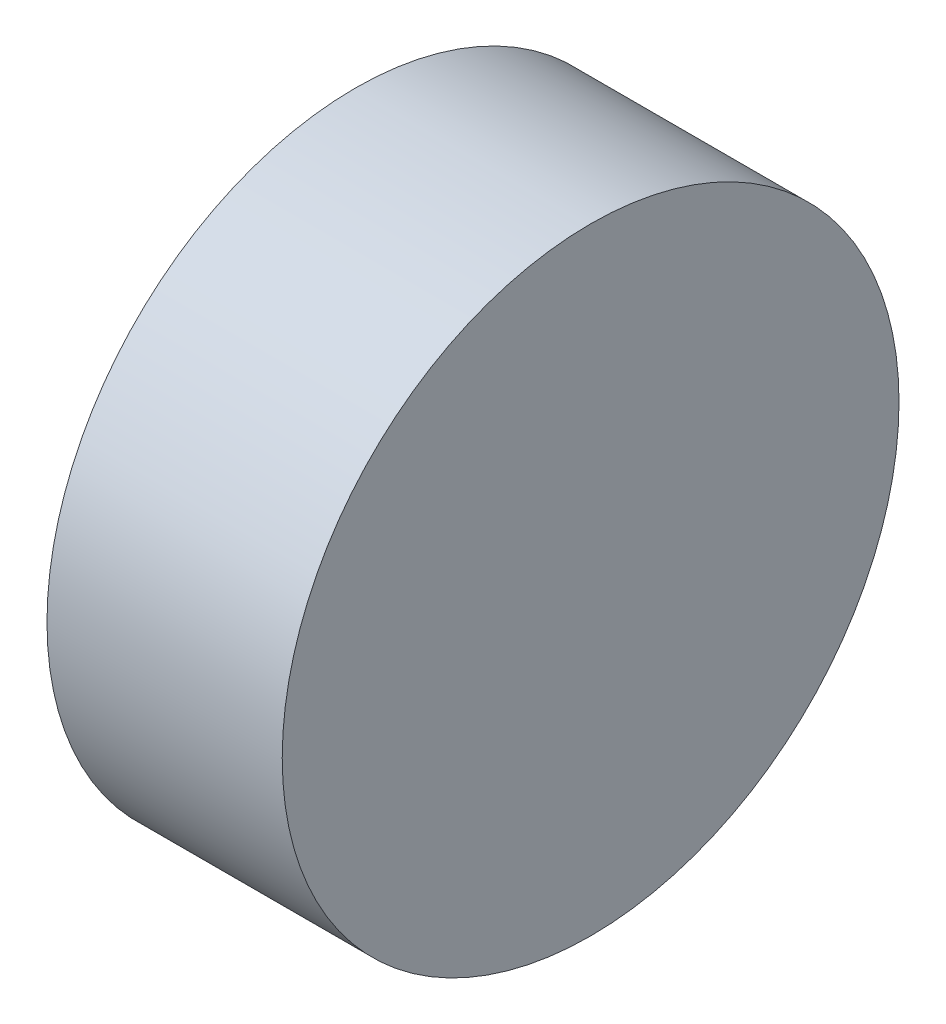
SolidWorks part; units mm, degrees
ref_plane "Front Plane" through (0, 0, 0) normal (0, 0, 1) x (1, 0, 0)
ref_plane "Top Plane" through (0, 0, 0) normal (0, 1, 0) x (1, 0, 0)
ref_plane "Right Plane" through (0, 0, 0) normal (1, 0, 0) x (0, 0, -1)
sketch "Sketch1" plane through (0, 0, 0) normal (1, 0, 0) x (0, 0, -1)
  circle A0 centre (0, 0) radius 33.3
  dimension "D1" = 66.6
extrude "Boss-Extrude1" add sketch "Sketch1" along normal blind 12.7 and the other way blind 12.7
